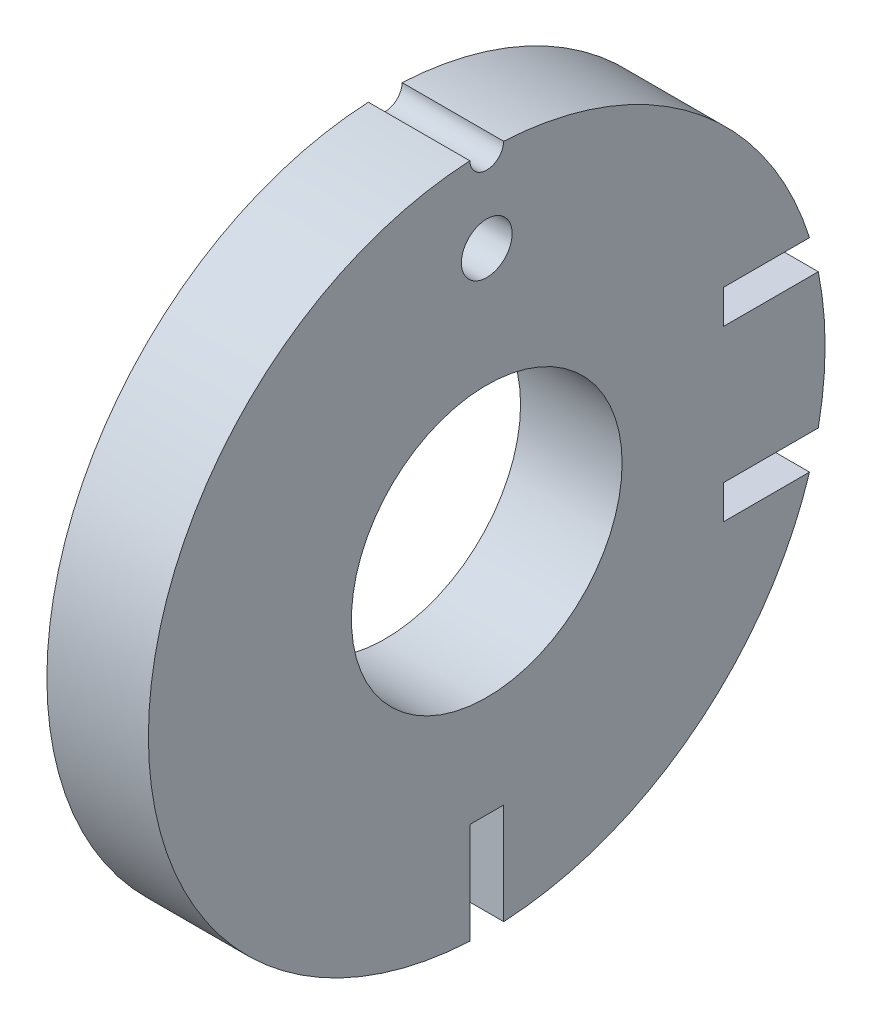
SolidWorks part; units mm, degrees
ref_plane "Front Plane" through (0, 0, 0) normal (0, 0, 1) x (1, 0, 0)
ref_plane "Top Plane" through (0, 0, 0) normal (0, 1, 0) x (1, 0, 0)
ref_plane "Right Plane" through (0, 0, 0) normal (1, 0, 0) x (0, 0, -1)
sketch "Sketch1" plane through (0, 0, 0) normal (1, 0, 0) x (0, 0, -1)
  circle A0 centre (0, 0) radius 10
  circle A1 centre (0, 0) radius 4
  dimension "D1" = 8
  dimension "D2" = 20
extrude "Boss-Extrude1" add sketch "Sketch1" along normal blind 3
sketch "Sketch2" plane through (3, 0, 0) normal (1, 0, 0) x (0, 0, -1)
  line L1 (7, 3) -> (12.7097, 3)
  line L2 (7, 3) -> (7, 2)
  line L3 (7, 2) -> (12.7097, 2)
  line L4 (12.7097, 3) -> (12.7097, 2)
  line L5 (7, -2) -> (12.7097, -2)
  line L6 (7, -2) -> (7, -3)
  line L7 (7, -3) -> (12.7097, -3)
  line L8 (12.7097, -2) -> (12.7097, -3)
  line L9 (-0.5, -7) -> (0.5, -7)
  line L10 (-0.5, -7) -> (-0.5, -11.5058)
  line L11 (-0.5, -11.5058) -> (0.5, -11.5058)
  line L12 (0.5, -7) -> (0.5, -11.5058)
  circle A0 centre (0, 7.5) radius 0.75
  circle A1 centre (0, 0) radius 10 construction
  circle A2 centre (0, 10) radius 0.5
  dimension "D1" = 1.5
  dimension "D3" = 1
  dimension "D12" = 0.5
  dimension "D2" = 7.5
  dimension "D4" = 1
  dimension "D5" = 1
  dimension "D6" = 1
  dimension "D7" = 7
  dimension "D8" = 7
  dimension "D9" = 7
  dimension "D10" = 2
  dimension "D11" = 2
extrude "Cut-Extrude1" cut sketch "Sketch2" against normal blind 3
